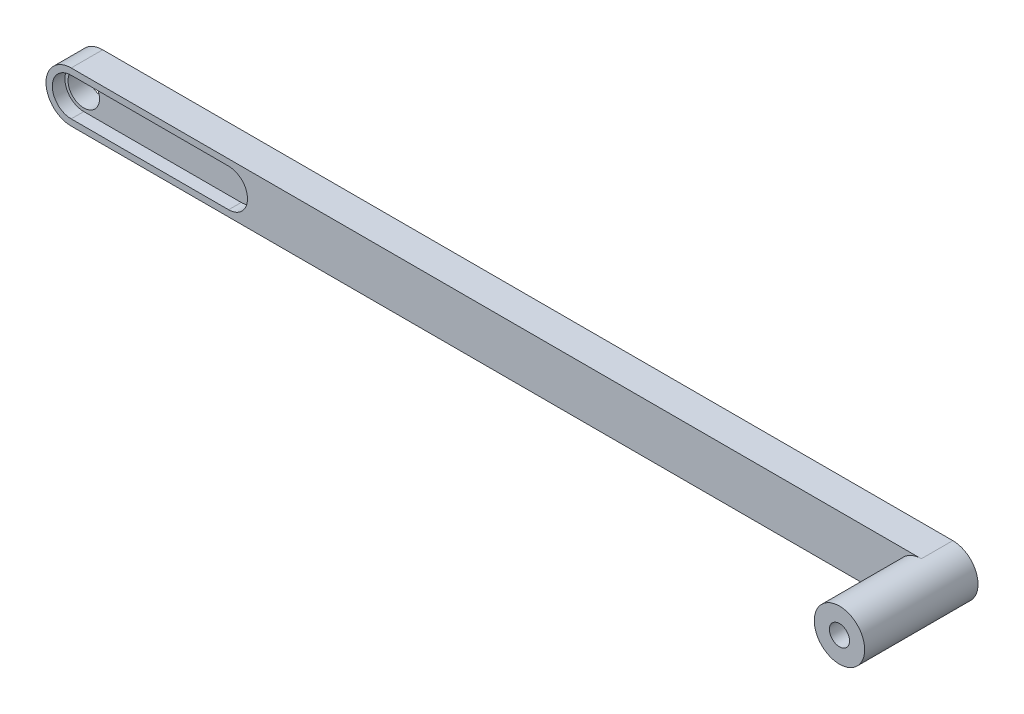
SolidWorks part; units mm, degrees
ref_plane "Front Plane" through (0, 0, 0) normal (0, 0, 1) x (1, 0, 0)
ref_plane "Top Plane" through (0, 0, 0) normal (0, 1, 0) x (1, 0, 0)
ref_plane "Right Plane" through (0, 0, 0) normal (1, 0, 0) x (0, 0, -1)
sketch "Sketch2" plane through (0, 0, 0) normal (0, 0, 1) x (1, 0, 0)
  line L0 (0, 0) -> (135, 0) construction
  line L1 (0, 4) -> (135, 4)
  line L2 (0, -4) -> (135, -4)
  arc A0 (0, 4) -> (0, -4) centre (0, 0) ccw
  arc A1 (135, -4) -> (135, 4) centre (135, 0) ccw
  circle A2 centre (0, 0) radius 2.5
  circle A3 centre (135, 0) radius 1.6
  point P3 (67.5, 0)
  dimension "D1" = 5
  dimension "D2" = 4
  dimension "D3" = 135
  dimension "D4" = 3.2
extrude "Boss-Extrude1" add sketch "Sketch2" along normal blind 5
sketch "Sketch3" plane through (0, 0, 5) normal (0, 0, 1) x (1, 0, 0)
  line L0 (0, -4) -> (135, -4) construction
  line L1 (135, 4) -> (0, 4) construction
  arc A0 (135, -4) -> (135, 4) centre (135, 0) ccw construction
  circle A1 centre (135, 0) radius 1.6 construction
  arc A2 (0, 4) -> (0, -4) centre (0, 0) ccw construction
  circle A3 centre (0, 0) radius 2.5 construction
  arc A4 (135, -4) -> (135, 4) centre (135, 0) ccw
  circle A5 centre (135, 0) radius 1.6
  arc A6 (0, 4) -> (0, -4) centre (0, 0) ccw
  circle A7 centre (0, 0) radius 2.5
  arc A8 (135, 4) -> (135, -4) centre (135, 0) ccw
  arc A9 (0, -4) -> (0, 4) centre (0, 0) ccw
  arc M4 (135, -4) -> (135, 4) centre (135, 0) ccw
  circle M6 centre (135, 0) radius 1.6
extrude "Boss-Extrude2" add sketch "Sketch3" along normal blind 13 contours A8 M4 M6 region at (131.1131, 0, 5)
sketch "Sketch4" plane through (0, 0, 5) normal (0, 0, 1) x (1, 0, 0)
  line L0 (0, 0) -> (25, 0) construction
  line L1 (0, 3) -> (25, 3)
  line L2 (0, -3) -> (25, -3)
  arc A0 (0, 3) -> (0, -3) centre (0, 0) ccw
  arc A1 (25, -3) -> (25, 3) centre (25, 0) ccw
  point P3 (12.5, 0)
  dimension "D2" = 3
  dimension "D1" = 25
extrude "Cut-Extrude1" cut sketch "Sketch4" against normal blind 2
